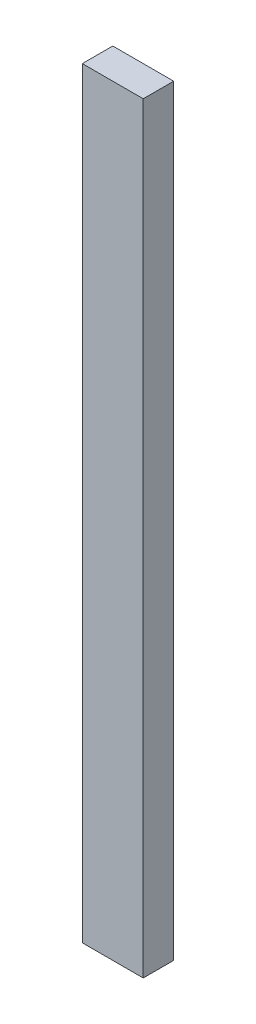
SolidWorks part; units mm, degrees
ref_plane "Спереди" through (0, 0, 0) normal (0, 0, 1) x (1, 0, 0)
ref_plane "Сверху" through (0, 0, 0) normal (0, 1, 0) x (1, 0, 0)
ref_plane "Справа" through (0, 0, 0) normal (1, 0, 0) x (0, 0, -1)
sketch "Эскиз1" plane through (0, 0, 0) normal (0, 1, 0) x (1, 0, 0)
  line L1 (0, 0) -> (40, 0)
  line L2 (0, 0) -> (0, 20)
  line L3 (0, 20) -> (40, 20)
  line L4 (40, 0) -> (40, 20)
  dimension "D1" = 20
  dimension "D2" = 40
extrude "Бобышка-Вытянуть1" add sketch "Эскиз1" along normal blind 500
